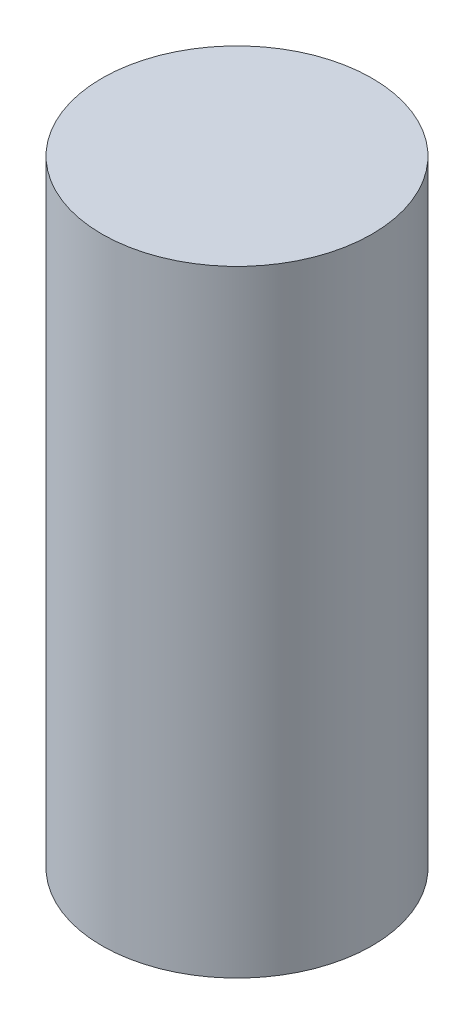
SolidWorks part; units mm, degrees
ref_plane "前视基准面" through (0, 0, 0) normal (0, 0, 1) x (1, 0, 0)
ref_plane "上视基准面" through (0, 0, 0) normal (0, 1, 0) x (1, 0, 0)
ref_plane "右视基准面" through (0, 0, 0) normal (1, 0, 0) x (0, 0, -1)
other "Configuration Table"
sketch "草图1" plane through (0, 0, 0) normal (0, 1, 0) x (1, 0, 0)
  circle A0 centre (0, 0) radius 13.585
  dimension "D1" = 27.17
extrude "凸台-拉伸1" add sketch "草图1" along normal blind 62
